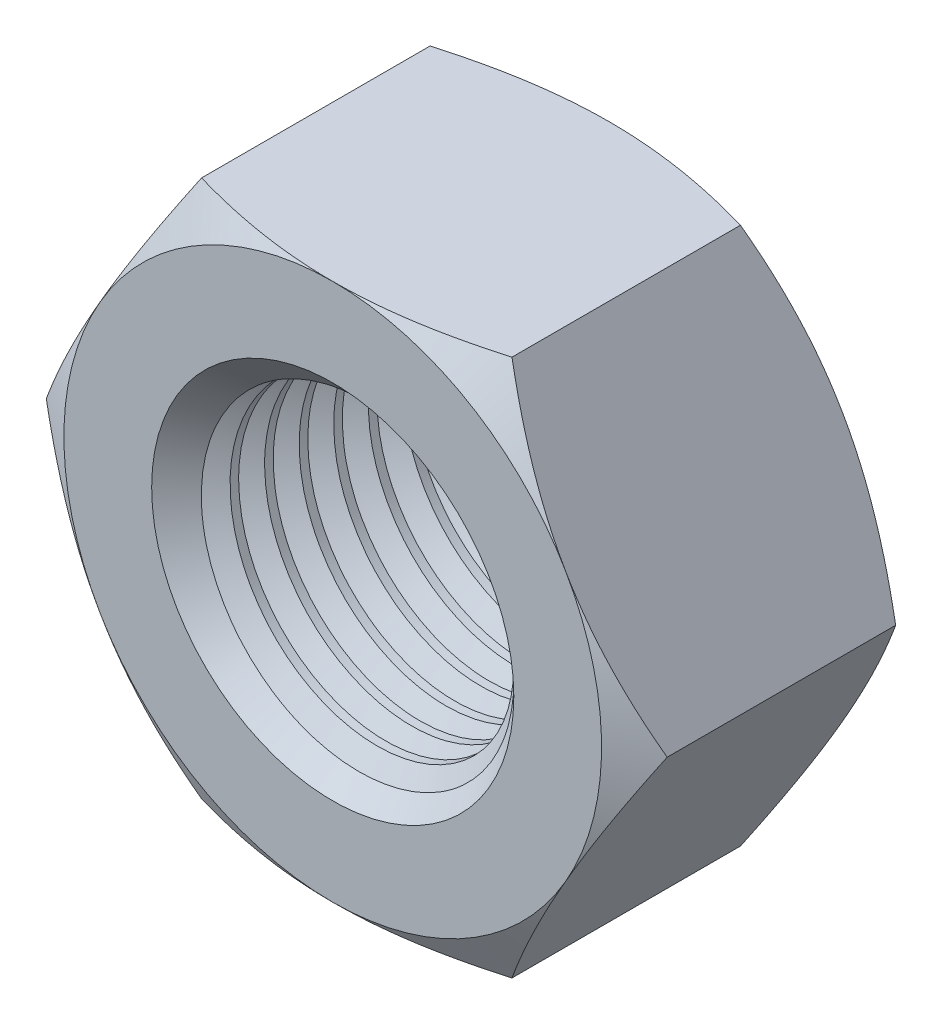
SolidWorks part; units mm, degrees
ref_plane "Front" through (0, 0, 0) normal (0, 0, 1) x (1, 0, 0)
ref_plane "Top" through (0, 0, 0) normal (0, 1, 0) x (1, 0, 0)
ref_plane "Right" through (0, 0, 0) normal (1, 0, 0) x (0, 0, -1)
sketch "Çizim1" plane through (0, 0, 0) normal (0, 0, 1) x (1, 0, 0)
  line L1 (40.4145, 0) -> (20.2073, 35)
  line L2 (20.2073, 35) -> (-20.2073, 35)
  line L3 (-20.2073, 35) -> (-40.4145, 0)
  line L4 (-40.4145, 0) -> (-20.2073, -35)
  line L5 (-20.2073, -35) -> (20.2073, -35)
  line L6 (20.2073, -35) -> (40.4145, 0)
  circle A0 centre (0, 0) radius 35 construction
  point P1 (0, 0)
  dimension "D1" = 70
extrude "Yükseklik-Ekstrüzyon1" add sketch "Çizim1" along normal blind 36
sketch "Çizim2" plane through (0, 0, 36) normal (0, 0, 1) x (1, 0, 0)
  circle A0 centre (0, 0) radius 35
extrude "Kes-Ekstrüzyon1" cut sketch "Çizim2" against normal blind 36 draft 60 flip side to cut
sketch "Çizim3" plane through (0, 0, 0) normal (0, 0, -1) x (-1, 0, 0)
  circle A0 centre (0, 0) radius 35
extrude "Kes-Ekstrüzyon2" cut sketch "Çizim3" against normal blind 36 draft 60 flip side to cut
sketch "Çizim4" plane through (0, 0, 0) normal (0, 0, -1) x (-1, 0, 0)
  circle A0 centre (0, 0) radius 19.575
  dimension "D1" = 39.15
extrude "Kes-Ekstrüzyon3" cut sketch "Çizim4" against normal blind 36
chamfer "Pah1" distance 4 angle 45 2 edges at (-19.575, 0, 36) (-19.575, 0, 0)
sketch "Çizim5" plane through (0, 0, 36) normal (0, 0, 1) x (1, 0, 0)
  circle A0 centre (0, 0) radius 19.575
curve "Helis/Spiral1" pitch 4.5 height 40 radius 19.575 centre (0, 0, 36) axis (0, 0, -1) start towards (-1, 0, 0)
ref_plane "Düzlem1" through (-14.9953, -12.5826, -4) normal (-0.6424, 0.7655, -0.0366) x (0.7664, 0.6416, -0.0306)
sketch "Çizim6" plane through (-14.9953, -12.5826, -4) normal (-0.6424, 0.7655, -0.0366) x (0.7664, 0.6416, -0.0306)
  line L0 (0.9651, 2.2459) -> (0.9651, -2.2459)
  line L1 (-2.925, 0) -> (0.9651, -2.2459)
  line L3 (0.9651, 2.2459) -> (-2.925, 0)
  line L5 (1.4625, 0) -> (1.4625, 2.5331) [skipped]
  circle A0 centre (0, 0) radius 1.4625 construction
  dimension "D1" = 2.925
sweep "Kes-Süpür1" cut profiles "Çizim6" path "Helis/Spiral1"
